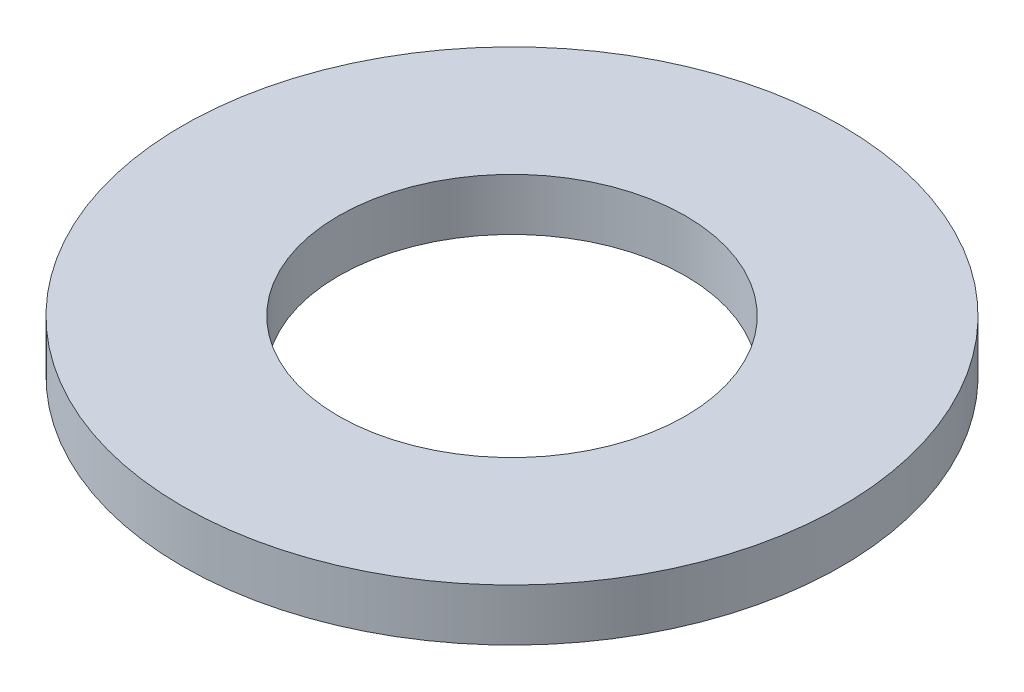
SolidWorks part; units mm, degrees
ref_plane "Front Plane" through (0, 0, 0) normal (0, 0, 1) x (1, 0, 0)
ref_plane "Top Plane" through (0, 0, 0) normal (0, 1, 0) x (1, 0, 0)
ref_plane "Right Plane" through (0, 0, 0) normal (1, 0, 0) x (0, 0, -1)
sketch "Sketch1" plane through (0, 0, 0) normal (0, 1, 0) x (1, 0, 0)
  circle A0 centre (0, 0) radius 95
  dimension "FLANGE_OD" = 190
extrude "Boss-Extrude1" add sketch "Sketch1" along normal blind 15
sketch "Sketch2" plane through (0, 0, 0) normal (0, 1, 0) x (1, 0, 0)
  circle A0 centre (0, 0) radius 50
  dimension "BORE_D" = 100
extrude "Cut-Extrude1" cut sketch "Sketch2" along normal through all
sketch "Sketch3" plane through (0, 15, 0) normal (0, 1, 0) x (1, 0, 0)
  circle A0 centre (0, 0) radius 30.9977 construction
  circle A1 centre (-30.9977, 0) radius 6.1624
  dimension "BOLT_D" = 12.3247
  dimension "BOLT_PCD" = 61.9954
extrude "Cut-Extrude2" cut sketch "Sketch3" against normal blind 14.4601 rebuild error yes
pattern_circular "CirPattern1" count 6 over 360 rebuild error yes
